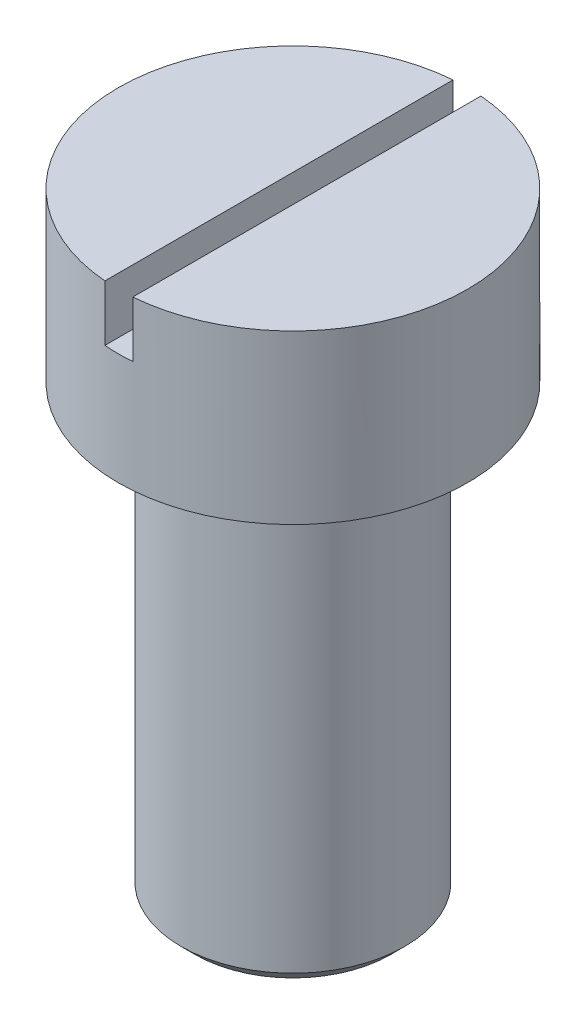
SolidWorks part; units mm, degrees
ref_plane "Ön Düzlem" through (0, 0, 0) normal (0, 0, 1) x (1, 0, 0)
ref_plane "Üst Düzlem" through (0, 0, 0) normal (0, 1, 0) x (1, 0, 0)
ref_plane "Sağ Düzlem" through (0, 0, 0) normal (1, 0, 0) x (0, 0, -1)
sketch "Çizim3" plane through (0, 0, 0) normal (0, 1, 0) x (1, 0, 0)
  circle A0 centre (0, 0) radius 12.5
  circle A1 centre (0, 0) radius 8
extrude "Yükseklik-Ekstrüzyon1" add sketch "Çizim3" along normal blind 12 contours A1 | A0 A1 region at (-12.1464, 0, 0) region at (0, 0, 0)
extrude "Yükseklik-Ekstrüzyon2" add sketch "Çizim3<3>" against normal blind 32 contours A1 region at (0, 0, 0)
sketch "Çizim3<3>" plane through (0, 0, 0) normal (0, 1, 0) x (1, 0, 0) same geometry as "Çizim3"
chamfer "Pah1" distance 1 angle 45 1 edges at (0, -32, 8)
cosmetic thread "Kozmetik Diş Açma1" parameters "D1"=25, "D2"=13.797
sketch "Çizim4" plane through (0, 12, 0) normal (0, 1, 0) x (1, 0, 0)
  line L1 (-1, -12.5) -> (1, -12.5)
  line L2 (-1, -12.5) -> (-1, 12.5)
  line L3 (-1, 12.5) -> (1, 12.5)
  line L4 (1, -12.5) -> (1, 12.5)
  line L5 (-1, -12.5) -> (1, 12.5) construction
  line L6 (-1, 12.5) -> (1, -12.5) construction
  circle A0 centre (0, 0) radius 12.5 construction
  point P0 (0, 0)
  dimension "D1" = 2
extrude "Kes-Ekstrüzyon1" cut sketch "Çizim4" against normal blind 4 and the other way through all
